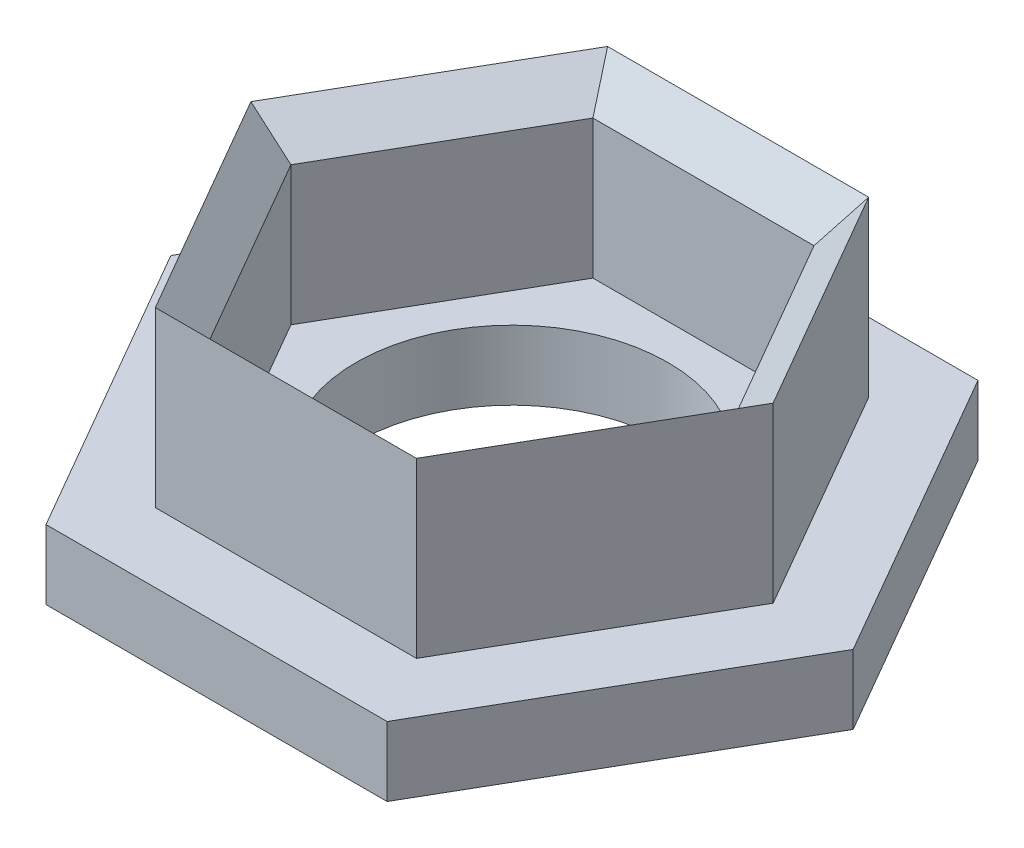
SolidWorks part; units mm, degrees
ref_plane "Front Plane" through (0, 0, 0) normal (0, 0, 1) x (1, 0, 0)
ref_plane "Top Plane" through (0, 0, 0) normal (0, 1, 0) x (1, 0, 0)
ref_plane "Right Plane" through (0, 0, 0) normal (1, 0, 0) x (0, 0, -1)
sketch "Sketch2" plane through (0, 0, 0) normal (0, -1, 0) x (1, 0, 0)
  line L12 (-4.9219, -8.525) -> (4.9219, -8.525)
  line L13 (4.9219, -8.525) -> (9.8438, 0)
  line L14 (9.8438, 0) -> (4.9219, 8.525)
  line L15 (4.9219, 8.525) -> (-4.9219, 8.525)
  line L16 (-4.9219, 8.525) -> (-9.8438, 0)
  line L17 (-9.8438, 0) -> (-4.9219, -8.525)
  line L18 (-4.9219, -8.525) -> (4.9219, -8.525)
  line L19 (4.9219, -8.525) -> (9.8438, 0)
  line L20 (9.8438, 0) -> (4.9219, 8.525)
  line L21 (4.9219, 8.525) -> (-4.9219, 8.525)
  line L22 (-4.9219, 8.525) -> (-9.8438, 0)
  line L23 (-9.8438, 0) -> (-4.9219, -8.525)
  circle A0 centre (0, 0) radius 4.5
  dimension "D1" = 2
extrude "Boss-Extrude1" add sketch "Sketch2" along normal blind 2
sketch "Sketch3" plane through (0, 0, 0) normal (0, -1, 0) x (1, 0, 0)
  line L6 (7.5344, 0) -> (3.7672, 6.525)
  line L7 (3.7672, 6.525) -> (-3.7672, 6.525)
  line L8 (-3.7672, 6.525) -> (-7.5344, 0)
  line L9 (-7.5344, 0) -> (-3.7672, -6.525)
  line L10 (-3.7672, -6.525) -> (3.7672, -6.525)
  line L11 (3.7672, -6.525) -> (7.5344, 0)
  line L12 (3.1899, 5.525) -> (-3.1899, 5.525)
  line L13 (6.3797, 0) -> (3.1899, 5.525)
  line L14 (3.1899, -5.525) -> (6.3797, 0)
  line L15 (-3.1899, -5.525) -> (3.1899, -5.525)
  line L16 (-6.3797, 0) -> (-3.1899, -5.525)
  line L17 (-3.1899, 5.525) -> (-6.3797, 0)
  line L18 (3.1899, 5.525) -> (-3.1899, 5.525)
  line L19 (6.3797, 0) -> (3.1899, 5.525)
  line L20 (3.1899, -5.525) -> (6.3797, 0)
  line L21 (-3.1899, -5.525) -> (3.1899, -5.525)
  line L22 (-6.3797, 0) -> (-3.1899, -5.525)
  line L23 (-3.1899, 5.525) -> (-6.3797, 0)
  dimension "D1" = 3
  dimension "D2" = 1
extrude "Boss-Extrude2" add sketch "Sketch3" against normal blind 5
chamfer "Chamfer1" distance 1 angle 45 6 edges at (0, 5, 5.525) (-4.7848, 5, 2.7625) (4.7848, 5, 2.7625) (4.7848, 5, -2.7625) (0, 5, -5.525) (-4.7848, 5, -2.7625)
